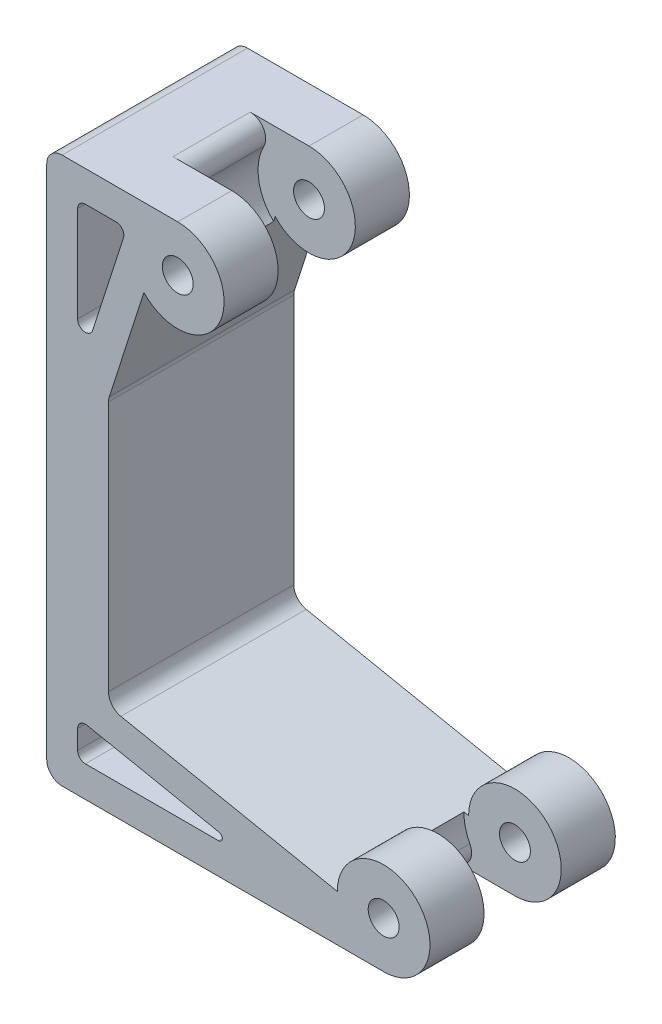
SolidWorks part; units mm, degrees
ref_plane "Front Plane" through (0, 0, 0) normal (0, 0, 1) x (1, 0, 0)
ref_plane "Top Plane" through (0, 0, 0) normal (0, 1, 0) x (1, 0, 0)
ref_plane "Right Plane" through (0, 0, 0) normal (1, 0, 0) x (0, 0, -1)
sketch "Sketch1" plane through (0, 0, 0) normal (0, 0, 1) x (1, 0, 0)
  line L0 (0, 0) -> (21.8174, 0)
  line L2 (0, 0) -> (0, 35.3819)
  line L3 (0, 35.3819) -> (8.4836, 35.3819)
  line L5 (6.2976, 30.3272) -> (4, 23.2001)
  line L6 (4, 23.2001) -> (4, 5.9735)
  line L7 (4, 5.9735) -> (18.8174, 3)
  line L11 (8.4836, 32.3819) -> (21.8174, 3) construction
  line L12 (5.181, 33.3819) -> (2, 33.3819)
  line L13 (2, 33.3819) -> (2, 23.5145)
  line L14 (2, 23.5145) -> (5.181, 33.3819)
  line L15 (8.4836, 32.3819) -> (8.4836, 5.1119) construction
  line L16 (8.4836, 5.1119) -> (21.8174, 3) construction
  line L17 (8.4836, 5.1119) -> (8.4836, -11.812) construction
  line L18 (2, 2) -> (2, 4.335)
  line L19 (2, 4.335) -> (13.6355, 2)
  line L20 (13.6355, 2) -> (2, 2)
  arc A0 (21.8174, 0) -> (18.8174, 3) centre (21.8174, 3) ccw
  arc A1 (8.4836, 35.3819) -> (6.2976, 30.3272) centre (8.4836, 32.3819) cw
  circle A2 centre (8.4836, 32.3819) radius 1
  circle A3 centre (21.8174, 3) radius 1
  dimension "D1" = 2
  dimension "D3" = 3
  dimension "D2" = 4
  dimension "D6" = 2
  dimension "D4" = 27.27
  dimension "D5" = 13.5
  dimension "D8" = 81
  dimension "D9" = 2
  dimension "D10" = 2
  dimension "D11" = 2
  dimension "D7" = 2
extrude "Boss-Extrude1" add sketch "Sketch1" along normal blind 12
ref_plane "midplane" through (0, 0, 6) normal (0, 0, 1) x (1, 0, 0)
sketch "Sketch2" plane through (0, 0, 6) normal (0, 0, 1) x (1, 0, 0)
  circle A0 centre (8.4836, 32.3819) radius 3.3
  circle A1 centre (21.8174, 3) radius 3.3
  dimension "D1" = 6.6
extrude "Cut-Extrude1" cut sketch "Sketch2" against normal blind 2.5 and the other way blind 2.5
fillet "Fillet1" radius 1 2 edges at (0, 0, 6) (0, 35.3819, 6)
fillet "Fillet2" radius 1 2 edges at (4, 5.9735, 6) (4, 23.2001, 6)
fillet "Fillet3" radius 1 2 edges at (7.1088, 35.3819, 6) (20.4426, 0, 6)
fillet "Fillet4" radius 0.5 5 edges at (2, 23.5145, 6) (5.181, 33.3819, 6) (2, 33.3819, 6) (2, 2, 6) (2, 4.335, 6)
fillet "Fillet5" radius 0.25 1 edges at (13.6355, 2, 6)
equation "\"axle-diameter\"=2"
equation "\"D1@Sketch1\"=\"axle-diameter\""
equation "\"switch-thickness\"=12"
equation "\"D1@Boss-Extrude1\"=\"switch-thickness\""
equation "\"base-width\"=4.0"
equation "\"D2@Sketch1\"=\"base-width\""
equation "\"axle-bushing-radius\"=3"
equation "\"D3@Sketch1\"= \"axle-bushing-radius\""
equation "\"D1@Sketch2\"=\"axle-bushing-radius\"*2.2"
equation "\"D1@Cut-Extrude1\"=\"switch-thickness\"/6+\"clearance\""
equation "\"D2@Cut-Extrude1\"=\"switch-thickness\"/6+\"clearance\""
equation "\"clearance\"= 0.5"
equation "\"arm-width\"=3.0"
